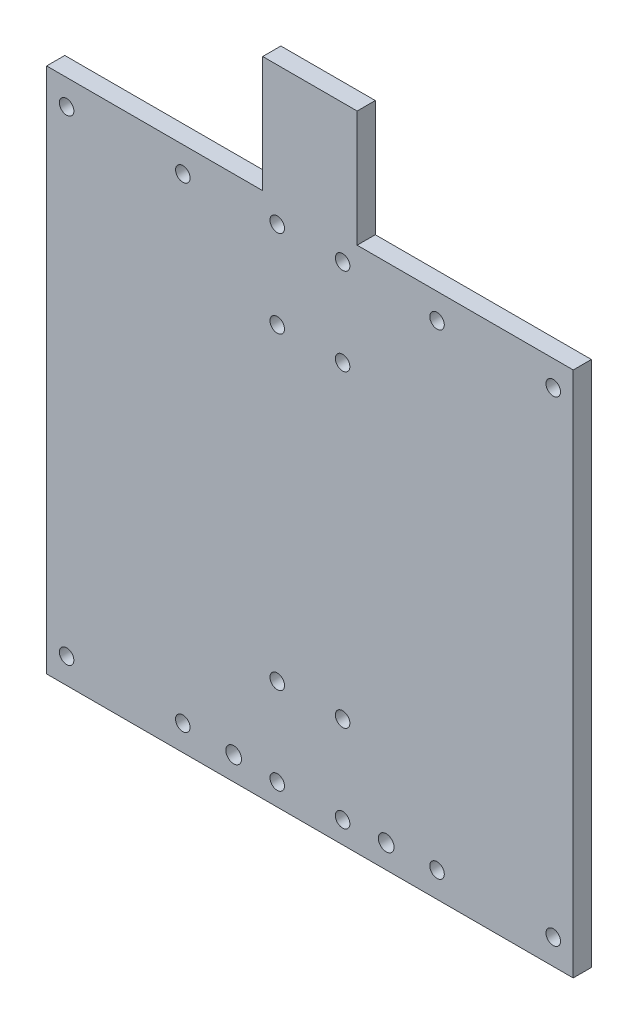
SolidWorks part; units mm, degrees
ref_plane "Front Plane" through (0, 0, 0) normal (0, 0, 1) x (1, 0, 0)
ref_plane "Top Plane" through (0, 0, 0) normal (0, 1, 0) x (1, 0, 0)
ref_plane "Right Plane" through (0, 0, 0) normal (1, 0, 0) x (0, 0, -1)
sketch "Sketch1" plane through (0, 0, 0) normal (0, 0, 1) x (1, 0, 0)
  line L0 (0, 0) -> (-72.5, 0) construction
  line L1 (-72.5, 72.5) -> (-13, 72.5)
  line L2 (-72.5, 72.5) -> (-72.5, -72.5)
  line L3 (-72.5, -72.5) -> (72.5, -72.5)
  line L4 (72.5, 72.5) -> (72.5, -72.5)
  line L5 (-72.5, 72.5) -> (72.5, -72.5) construction
  line L6 (-72.5, -72.5) -> (72.5, 72.5) construction
  line L7 (-13, 104.5) -> (13, 104.5)
  line L8 (-13, 104.5) -> (-13, 72.5)
  line L10 (13, 104.5) -> (13, 72.5)
  line L13 (0, 0) -> (0, -72.5) construction
  line L14 (13, 72.5) -> (72.5, 72.5)
  circle A0 centre (9, 42.5) radius 2
  circle A1 centre (-9, 42.5) radius 2
  circle A2 centre (-9, 66.5) radius 2
  circle A3 centre (9, 66.5) radius 2
  circle A4 centre (9, -66.5) radius 2
  circle A5 centre (-9, -66.5) radius 2
  circle A6 centre (-9, -42.5) radius 2
  circle A7 centre (9, -42.5) radius 2
  circle A8 centre (-21, -66) radius 2.1621
  circle A9 centre (21, -66) radius 2.1621
  circle A10 centre (35, -65.5) radius 2
  circle A11 centre (67, -65.5) radius 2
  circle A12 centre (-67, -65.5) radius 2
  circle A13 centre (-35, -65.5) radius 2
  circle A14 centre (-67, 65.5) radius 2
  circle A15 centre (-35, 65.5) radius 2
  circle A16 centre (67, 65.5) radius 2
  circle A17 centre (35, 65.5) radius 2
  point P0 (0, 0)
  dimension "D5" = 24
  dimension "D1" = 145
  dimension "D2" = 145
  dimension "D3" = 32
  dimension "D4" = 26
  dimension "D6" = 24
  dimension "D7" = 7
  dimension "D8" = 7
  dimension "D9" = 6
  dimension "D10" = 6.5
  dimension "D11" = 6.5
  dimension "D12" = 6
extrude "Boss-Extrude1" add sketch "Sketch1" along normal blind 5
